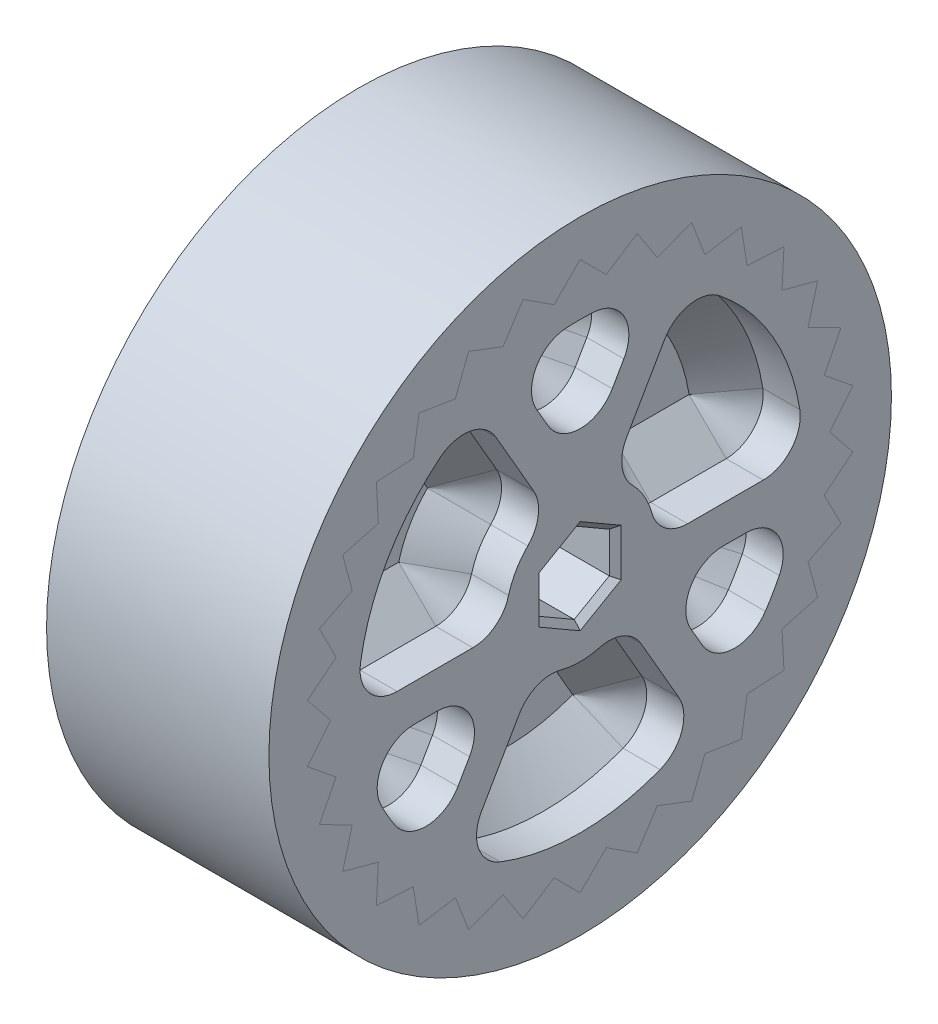
SolidWorks part; units mm, degrees
note: '?' marks a value the reader was unsure of.
other "WheelBody"
other "TPUOuter"
ref_plane "Front Plane" through (0, 0, 0) normal (0, 0, 1) x (1, 0, 0)
ref_plane "Top Plane" through (0, 0, 0) normal (0, 1, 0) x (1, 0, 0)
ref_plane "Right Plane" through (0, 0, 0) normal (1, 0, 0) x (0, 0, -1)
sketch "Sketch1" plane through (0, 0, 0) normal (1, 0, 0) x (0, 0, -1)
  circle A0 centre (0, 0) radius 25.4
  dimension "D1" = 50.8
extrude "Boss-Extrude2" add sketch "Sketch1" along normal mid plane 6.35
sketch "Sketch3" plane through (0, 0, 0) normal (1, 0, 0) x (0, 0, -1)
  circle A0 centre (0, 0) radius 6.35
  dimension "D1" = 12.7
extrude "Boss-Extrude3" add sketch "Sketch3" against normal mid plane 19.05
ref_axis "Axis1" through (0, 0, 0) along (1, 0, 0)?
sketch "Sketch5" plane through (9.525, 0, 0) normal (1, 0, 0) x (0, 0, -1)
  line L0 (0, 25.3821) -> (0, 34.0271) construction
  line L2 (-5.9601, 18.0936) -> (0, 7.7705)
  line L3 (-2.54, 5.8199) -> (-8.9033, 16.8414)
  line L5 (2.54, 5.8199) -> (8.9033, 16.8414)
  line L7 (0, 0) -> (23.8682, 8.6873) construction
  line L8 (17.9011, 6.5155) -> (23.8682, 8.6873)
  line L9 (8.9033, 16.8414) -> (12.08, 22.3436) construction
  line L10 (-18.046, 6.1028) -> (-23.9412, 8.4841)
  line L11 (-8.9033, 16.8414) -> (-12.08, 22.3436) construction
  line L12 (-2.54, 5.8199) -> (2.54, 5.8199)
  line L13 (0, 7.7705) -> (5.9601, 18.0936)
  arc A1 (-8.9033, 16.8414) -> (-18.046, 6.1028) centre (0, 0) ccw
  arc A4 (5.9601, 18.0936) -> (-5.9601, 18.0936) centre (0, 0) ccw
  arc A5 (-12.08, 22.3436) -> (12.08, 22.3436) centre (0, 0) cw
  circle A6 centre (0, 0) radius 25.4 construction
  arc A8 (-12.08, 22.3436) -> (-23.9412, 8.4841) centre (0, 0) ccw
  arc A11 (12.08, 22.3436) -> (23.8682, 8.6873) centre (0, 0) cw
  arc A12 (8.9033, 16.8414) -> (17.9011, 6.5155) centre (0, 0) cw
  circle A13 centre (0, 0) radius 6.35 construction
  circle A14 centre (0, 0) radius 6.35 construction
  dimension "D1" = 3.175
  dimension "D2" = 3.175
  dimension "D3" = 5.08
  dimension "D5" = 60
  dimension "D9" = 6.35
extrude "Boss-Extrude4" add sketch "Sketch5" against normal up to surface (19.05 mm away)
pattern_circular "CirPattern5" count 3 over 360 about axis through (0, 0, 0) along (1, 0, 0) of "Boss-Extrude4"
fillet "Fillet1" radius 3.175 21 edges at (6.35, -0.7102, 19.0368) (6.35, -0.7102, 6.3102) (6.35, -5.1096, 3.7702) (6.35, -16.1312, 10.1335) (6.35, -3.8852, 18.6496) (6.35, -14.2084, 12.6895) (6.35, -3.8852, 6.7294) (6.35, -16.1312, -10.1335) (6.35, -5.1096, -3.7702) (6.35, -0.7102, -6.3102) (6.35, -0.7102, -19.0368) (6.35, -14.2084, -12.6895) (6.35, -3.8852, -18.6496) (6.35, -3.8852, -6.7294) (6.35, 16.8414, -8.9033) (6.35, 5.8199, -2.54) (6.35, 5.8199, 2.54) (6.35, 16.8414, 8.9033) (6.35, 18.0936, -5.9601) (6.35, 18.0936, 5.9601) (6.35, 7.7705, 0)
fillet "Fillet2" radius 3.175 21 edges at (-6.35, -16.1312, 10.1335) (-6.35, -3.8852, 18.6496) (-6.35, -14.2084, 12.6895) (-6.35, -3.8852, 6.7294) (-6.35, -14.2084, -12.6895) (-6.35, -3.8852, -18.6496) (-6.35, -3.8852, -6.7294) (-6.35, -0.7102, 19.0368) (-6.35, -0.7102, 6.3102) (-6.35, -5.1096, 3.7702) (-6.35, -16.1312, -10.1335) (-6.35, -5.1096, -3.7702) (-6.35, -0.7102, -6.3102) (-6.35, -0.7102, -19.0368) (-6.35, 16.8414, 8.9033) (-6.35, 18.0936, -5.9601) (-6.35, 18.0936, 5.9601) (-6.35, 7.7705, 0) (-6.35, 16.8414, -8.9033) (-6.35, 5.8199, -2.54) (-6.35, 5.8199, 2.54)
sketch "Sketch6" plane through (9.525, 0, 0) normal (1, 0, 0) x (0, 0, -1)
  line L1 (0, 3.4641) -> (-3, 1.7321)
  line L2 (-3, 1.7321) -> (-3, -1.7321)
  line L3 (-3, -1.7321) -> (0, -3.4641)
  line L4 (0, -3.4641) -> (3, -1.7321)
  line L5 (3, -1.7321) -> (3, 1.7321)
  line L6 (3, 1.7321) -> (0, 3.4641)
  circle A0 centre (0, 0) radius 3 construction
  dimension "D1" = 6
extrude "Cut-Extrude2" cut sketch "Sketch6" against normal through all both and the other way through all
chamfer "Chamfer1" distance 3.175 angle 45 84 edges at (3.175, 13.3946, 3.2471) (3.175, 19.05, 0) (3.175, 13.3946, -3.2471) (3.175, 17.3443, -3.793) (3.175, 10.9455, 0) (3.175, 17.3443, 3.793) (3.175, -9.5094, 9.9765) (3.175, -9.525, 16.4978) (3.175, -3.8852, 13.2236) (3.175, -5.3873, 16.9171) (3.175, -5.4727, 9.479) (3.175, -11.957, 13.1241) (3.175, -3.8852, -13.2236) (3.175, -9.525, -16.4978) (3.175, -9.5094, -9.9765) (3.175, -11.957, -13.1241) (3.175, -5.4727, -9.479) (3.175, -5.3873, -16.9171) (3.175, 3.175, 5.4993) (3.175, -0.7102, 12.4415) (3.175, 11.1298, 5.6057) (3.175, 9.525, 16.4978) (3.175, 0.4013, 18.0956) (3.175, 15.4705, 9.3953) (3.175, 6.321, 3.587) (3.175, -0.0541, 7.2677) (3.175, -0.7102, -12.4415) (3.175, 3.175, -5.4993) (3.175, 9.525, -16.4978) (3.175, 11.1298, -5.6057) (3.175, 15.4705, -9.3953) (3.175, 0.4013, -18.0956) (3.175, 6.321, -3.587) (3.175, -0.0541, -7.2677) (3.175, -6.35, 0) (3.175, -10.4196, -6.8358) (3.175, -10.4196, 6.8358) (3.175, -19.05, 0) (3.175, -15.8719, -8.7002) (3.175, -15.8719, 8.7002) (3.175, -6.267, 3.6807) (3.175, -6.267, -3.6807) (-3.175, 13.3946, 3.2471) (-3.175, 19.05, 0) (-3.175, 13.3946, -3.2471) (-3.175, 17.3443, -3.793) (-3.175, 10.9455, 0) (-3.175, 17.3443, 3.793) (-3.175, -3.8852, -13.2236) (-3.175, -9.525, -16.4978) (-3.175, -9.5094, -9.9765) (-3.175, -5.4727, -9.479) (-3.175, -11.957, -13.1241) (-3.175, -5.3873, -16.9171) (-3.175, -9.5094, 9.9765) (-3.175, -9.525, 16.4978) (-3.175, -3.8852, 13.2236) (-3.175, -5.4727, 9.479) (-3.175, -5.3873, 16.9171) (-3.175, -11.957, 13.1241) (-3.175, -0.7102, -12.4415) (-3.175, 3.175, -5.4993) (-3.175, 11.1298, -5.6057) (-3.175, 9.525, -16.4978) (-3.175, 15.4705, -9.3953) (-3.175, 0.4013, -18.0956) (-3.175, 6.321, -3.587) (-3.175, -0.0541, -7.2677) (-3.175, -10.4196, 6.8358) (-3.175, -6.35, 0) (-3.175, -10.4196, -6.8358) (-3.175, -19.05, 0) (-3.175, -15.8719, 8.7002) (-3.175, -15.8719, -8.7002) (-3.175, -6.267, -3.6807) (-3.175, -6.267, 3.6807) (-3.175, 11.1298, 5.6057) (-3.175, 3.175, 5.4993) (-3.175, -0.7102, 12.4415) (-3.175, 9.525, 16.4978) (-3.175, 15.4705, 9.3953) (-3.175, 0.4013, 18.0956) (-3.175, -0.0541, 7.2677) (-3.175, 6.321, 3.587)
chamfer "ShaftChamfer" distance 0.508 angle 45 12 edges at (9.525, 0, -3) (-9.525, 0, -3) (9.525, -2.5981, 1.5) (-9.525, -2.5981, 1.5) (9.525, -2.5981, -1.5) (-9.525, -2.5981, -1.5) (9.525, 0, 3) (-9.525, 0, 3) (9.525, 2.5981, 1.5) (-9.525, 2.5981, 1.5) (9.525, 2.5981, -1.5) (-9.525, 2.5981, -1.5)
sketch "Sketch8" plane through (-9.525, 0, 0) normal (-1, 0, 0) x (0, 0, 1)
  circle A0 centre (0, 0) radius 26.67
  circle A1 centre (0, 0) radius 12.7
  dimension "D1" = 53.34
  dimension "D2" = 25.4
extrude "Boss-Extrude5" add sketch "Sketch8" against normal up to surface (19.05 mm away) separate body
sketch "Sketch9" plane through (-9.525, 0, 0) normal (-1, 0, 0) x (0, 0, 1)
  line L0 (0, 0) -> (0, 23.495) construction
  line L1 (-2.54, 20.955) -> (0, 23.495)
  line L2 (0, 23.495) -> (2.54, 20.955)
  line L3 (2.54, 20.955) -> (0, 0)
  line L4 (-2.54, 20.955) -> (0, 0)
  line L5 (-6.766, 26.67) -> (10.6632, 26.67) construction
  circle A1 centre (0, 0) radius 26.67 construction
  dimension "D1" = 90
  dimension "D2" = 2.54
  dimension "D3" = 3.175
extrude "Cut-Extrude3" cut sketch "Sketch9" against normal through all both and the other way through all
pattern_circular "CirPattern9" count 30 over 360 about axis through (0, 0, 0) along (1, 0, 0) of "Cut-Extrude3"
sketch "Sketch10" plane through (9.525, 0, 0) normal (1, 0, 0) x (0, 0, -1)
  line L60 (4.8849, 22.9816) -> (2.2346, 21.2604)
  line L61 (6.606, 20.3313) -> (4.8849, 22.9816)
  line L62 (9.5563, 21.4638) -> (6.606, 20.3313)
  line L63 (10.6888, 18.5135) -> (9.5563, 21.4638)
  line L64 (13.81, 19.0079) -> (10.6888, 18.5135)
  line L65 (14.3044, 15.8866) -> (13.81, 19.0079)
  line L66 (17.4602, 15.7212) -> (14.3044, 15.8866)
  line L67 (17.2948, 12.5654) -> (17.4602, 15.7212)
  line L68 (20.3473, 11.7475) -> (17.2948, 12.5654)
  line L69 (19.5294, 8.695) -> (20.3473, 11.7475)
  line L70 (22.3451, 7.2604) -> (19.5294, 8.695)
  line L71 (20.9104, 4.4446) -> (22.3451, 7.2604)
  line L72 (23.3663, 2.4559) -> (20.9104, 4.4446)
  line L73 (21.3775, 0) -> (23.3663, 2.4559)
  line L74 (23.3663, -2.4559) -> (21.3775, 0)
  line L75 (20.9104, -4.4446) -> (23.3663, -2.4559)
  line L76 (22.3451, -7.2604) -> (20.9104, -4.4446)
  line L77 (19.5294, -8.695) -> (22.3451, -7.2604)
  line L78 (20.3473, -11.7475) -> (19.5294, -8.695)
  line L79 (17.2948, -12.5654) -> (20.3473, -11.7475)
  line L80 (17.4602, -15.7212) -> (17.2948, -12.5654)
  line L81 (14.3044, -15.8866) -> (17.4602, -15.7212)
  line L82 (13.81, -19.0079) -> (14.3044, -15.8866)
  line L83 (10.6888, -18.5135) -> (13.81, -19.0079)
  line L84 (9.5563, -21.4638) -> (10.6888, -18.5135)
  line L85 (6.606, -20.3313) -> (9.5563, -21.4638)
  line L86 (4.8849, -22.9816) -> (6.606, -20.3313)
  line L87 (2.2346, -21.2604) -> (4.8849, -22.9816)
  line L88 (0, -23.495) -> (2.2346, -21.2604)
  line L89 (-2.2346, -21.2604) -> (0, -23.495)
  line L90 (-4.8849, -22.9816) -> (-2.2346, -21.2604)
  line L91 (-6.606, -20.3313) -> (-4.8849, -22.9816)
  line L92 (-9.5563, -21.4638) -> (-6.606, -20.3313)
  line L93 (-10.6888, -18.5135) -> (-9.5563, -21.4638)
  line L94 (-13.81, -19.0079) -> (-10.6888, -18.5135)
  line L95 (-14.3044, -15.8866) -> (-13.81, -19.0079)
  line L96 (-17.4602, -15.7212) -> (-14.3044, -15.8866)
  line L97 (-17.2948, -12.5654) -> (-17.4602, -15.7212)
  line L98 (-20.3473, -11.7475) -> (-17.2948, -12.5654)
  line L99 (-19.5294, -8.695) -> (-20.3473, -11.7475)
  line L100 (-22.3451, -7.2604) -> (-19.5294, -8.695)
  line L101 (-20.9104, -4.4446) -> (-22.3451, -7.2604)
  line L102 (-23.3663, -2.4559) -> (-20.9104, -4.4446)
  line L103 (-21.3775, 0) -> (-23.3663, -2.4559)
  line L104 (-23.3663, 2.4559) -> (-21.3775, 0)
  line L105 (-20.9104, 4.4446) -> (-23.3663, 2.4559)
  line L106 (-22.3451, 7.2604) -> (-20.9104, 4.4446)
  line L107 (-19.5294, 8.695) -> (-22.3451, 7.2604)
  line L108 (-20.3473, 11.7475) -> (-19.5294, 8.695)
  line L109 (-17.2948, 12.5654) -> (-20.3473, 11.7475)
  line L110 (-17.4602, 15.7212) -> (-17.2948, 12.5654)
  line L111 (-14.3044, 15.8866) -> (-17.4602, 15.7212)
  line L112 (-13.81, 19.0079) -> (-14.3044, 15.8866)
  line L113 (-10.6888, 18.5135) -> (-13.81, 19.0079)
  line L114 (-9.5563, 21.4638) -> (-10.6888, 18.5135)
  line L115 (-6.606, 20.3313) -> (-9.5563, 21.4638)
  line L116 (-4.8849, 22.9816) -> (-6.606, 20.3313)
  line L117 (-2.2346, 21.2604) -> (-4.8849, 22.9816)
  line L118 (0, 23.495) -> (-2.2346, 21.2604)
  line L119 (2.2346, 21.2604) -> (0, 23.495)
  line L120 (4.8849, 22.9816) -> (2.2346, 21.2604)
  line L121 (6.606, 20.3313) -> (4.8849, 22.9816)
  line L122 (9.5563, 21.4638) -> (6.606, 20.3313)
  line L123 (10.6888, 18.5135) -> (9.5563, 21.4638)
  line L124 (13.81, 19.0079) -> (10.6888, 18.5135)
  line L125 (14.3044, 15.8866) -> (13.81, 19.0079)
  line L126 (17.4602, 15.7212) -> (14.3044, 15.8866)
  line L127 (17.2948, 12.5654) -> (17.4602, 15.7212)
  line L128 (20.3473, 11.7475) -> (17.2948, 12.5654)
  line L129 (19.5294, 8.695) -> (20.3473, 11.7475)
  line L130 (22.3451, 7.2604) -> (19.5294, 8.695)
  line L131 (20.9104, 4.4446) -> (22.3451, 7.2604)
  line L132 (23.3663, 2.4559) -> (20.9104, 4.4446)
  line L133 (21.3775, 0) -> (23.3663, 2.4559)
  line L134 (23.3663, -2.4559) -> (21.3775, 0)
  line L135 (20.9104, -4.4446) -> (23.3663, -2.4559)
  line L136 (22.3451, -7.2604) -> (20.9104, -4.4446)
  line L137 (19.5294, -8.695) -> (22.3451, -7.2604)
  line L138 (20.3473, -11.7475) -> (19.5294, -8.695)
  line L139 (17.2948, -12.5654) -> (20.3473, -11.7475)
  line L140 (17.4602, -15.7212) -> (17.2948, -12.5654)
  line L141 (14.3044, -15.8866) -> (17.4602, -15.7212)
  line L142 (13.81, -19.0079) -> (14.3044, -15.8866)
  line L143 (10.6888, -18.5135) -> (13.81, -19.0079)
  line L144 (9.5563, -21.4638) -> (10.6888, -18.5135)
  line L145 (6.606, -20.3313) -> (9.5563, -21.4638)
  line L146 (4.8849, -22.9816) -> (6.606, -20.3313)
  line L147 (2.2346, -21.2604) -> (4.8849, -22.9816)
  line L148 (0, -23.495) -> (2.2346, -21.2604)
  line L149 (-2.2346, -21.2604) -> (0, -23.495)
  line L150 (-4.8849, -22.9816) -> (-2.2346, -21.2604)
  line L151 (-6.606, -20.3313) -> (-4.8849, -22.9816)
  line L152 (-9.5563, -21.4638) -> (-6.606, -20.3313)
  line L153 (-10.6888, -18.5135) -> (-9.5563, -21.4638)
  line L154 (-13.81, -19.0079) -> (-10.6888, -18.5135)
  line L155 (-14.3044, -15.8866) -> (-13.81, -19.0079)
  line L156 (-17.4602, -15.7212) -> (-14.3044, -15.8866)
  line L157 (-17.2948, -12.5654) -> (-17.4602, -15.7212)
  line L158 (-20.3473, -11.7475) -> (-17.2948, -12.5654)
  line L159 (-19.5294, -8.695) -> (-20.3473, -11.7475)
  line L160 (-22.3451, -7.2604) -> (-19.5294, -8.695)
  line L161 (-20.9104, -4.4446) -> (-22.3451, -7.2604)
  line L162 (-23.3663, -2.4559) -> (-20.9104, -4.4446)
  line L163 (-21.3775, 0) -> (-23.3663, -2.4559)
  line L164 (-23.3663, 2.4559) -> (-21.3775, 0)
  line L165 (-20.9104, 4.4446) -> (-23.3663, 2.4559)
  line L166 (-22.3451, 7.2604) -> (-20.9104, 4.4446)
  line L167 (-19.5294, 8.695) -> (-22.3451, 7.2604)
  line L168 (-20.3473, 11.7475) -> (-19.5294, 8.695)
  line L169 (-17.2948, 12.5654) -> (-20.3473, 11.7475)
  line L170 (-17.4602, 15.7212) -> (-17.2948, 12.5654)
  line L171 (-14.3044, 15.8866) -> (-17.4602, 15.7212)
  line L172 (-13.81, 19.0079) -> (-14.3044, 15.8866)
  line L173 (-10.6888, 18.5135) -> (-13.81, 19.0079)
  line L174 (-9.5563, 21.4638) -> (-10.6888, 18.5135)
  line L175 (-6.606, 20.3313) -> (-9.5563, 21.4638)
  line L176 (-4.8849, 22.9816) -> (-6.606, 20.3313)
  line L177 (-2.2346, 21.2604) -> (-4.8849, 22.9816)
  line L178 (0, 23.495) -> (-2.2346, 21.2604)
  line L179 (2.2346, 21.2604) -> (0, 23.495)
  circle A1 centre (0, 0) radius 26.67
  circle A2 centre (0, 0) radius 26.67
  dimension "D1" = 0
  dimension "D2" = 0
extrude "Cut-Extrude4" cut sketch "Sketch10" against normal through all both and the other way through all
